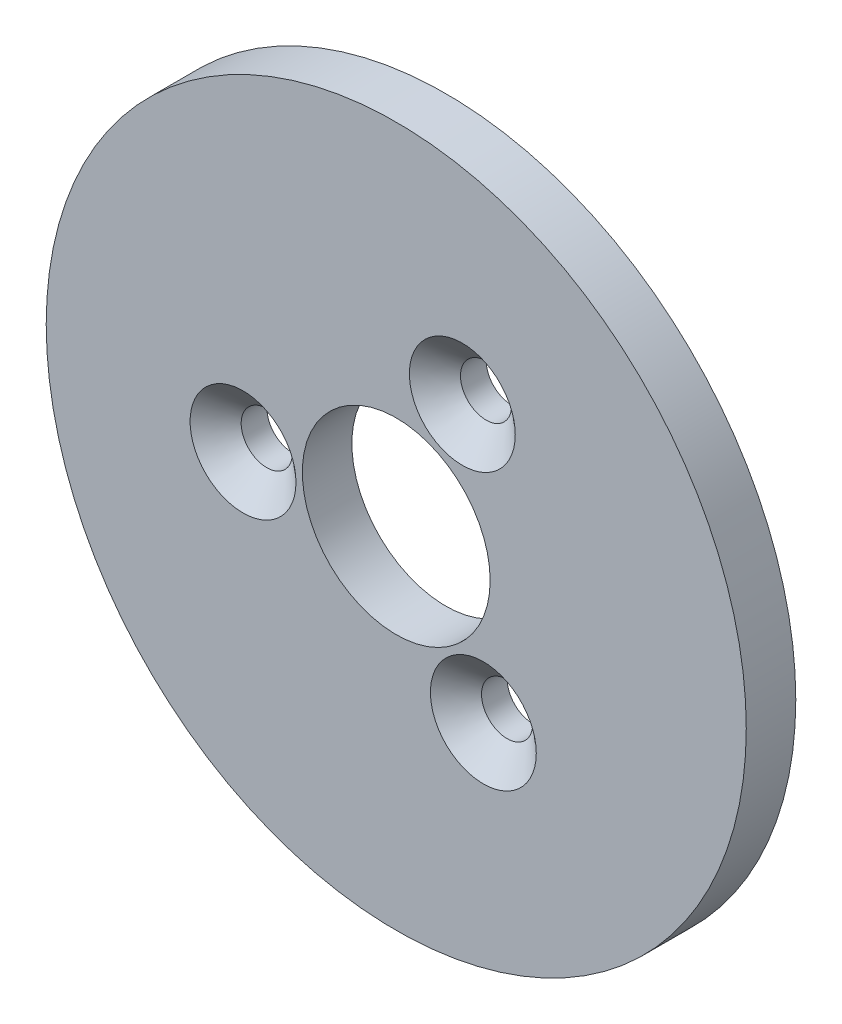
SolidWorks part; units mm, degrees
material "Acrylic (Medium-high impact)"
ref_plane "Front Plane" through (0, 0, 0) normal (0, 0, 1) x (1, 0, 0)
ref_plane "Top Plane" through (0, 0, 0) normal (0, 1, 0) x (1, 0, 0)
ref_plane "Right Plane" through (0, 0, 0) normal (1, 0, 0) x (0, 0, -1)
sketch "Sketch1" plane through (0, 0, 0) normal (0, 0, 1) x (1, 0, 0)
  circle A0 centre (0, 0) radius 20.5
  dimension "D1" = 41
extrude "Boss-Extrude1" add sketch "Sketch1" along normal blind 2.9
sketch "Sketch2" plane through (0, 0, 2.9) normal (0, 0, 1) x (1, 0, 0)
  circle A3 centre (-8.9719, -0.7111) radius 1.5
  circle A4 centre (-8.9719, -0.7111) radius 1.5
  circle A5 centre (5.1018, -7.4143) radius 1.5
  circle A6 centre (5.1018, -7.4143) radius 1.5
  circle A7 centre (3.8701, 8.1254) radius 1.5
  circle A8 centre (3.8701, 8.1254) radius 1.5
  dimension "D2" = 0
  dimension "D3" = 0
  dimension "D4" = 0
extrude "Cut-Extrude1" cut sketch "Sketch2" against normal through all
chamfer "Chamfer1" distance 1.6 angle 41 3 edges at (-7.4719, -0.7111, 2.9) (5.3701, 8.1254, 2.9) (6.6018, -7.4143, 2.9) first distance on face at (6.6018, -7.4143, 2.9)
sketch "Sketch3" plane through (0, 0, 2.9) normal (0, 0, 1) x (1, 0, 0)
  circle A1 centre (0, 0) radius 5.5
  circle A2 centre (0, 0) radius 5.5
  dimension "D1" = 0
extrude "Cut-Extrude2" cut sketch "Sketch3" against normal through all
equation "\"smallPulleyTeeth\"= 15"
equation "\"largePulleyTeeth\"= 30"
equation "\"eighthThick\"= 2.9mm"
equation "\"sixteenthThick\"= 1.7mm"
equation "\"quarterThick\"=6.0mm"
equation "\"OD\"= 145mm"
equation "\"puckAngle\"= 60.5deg"
equation "\"puckDiam\"= 76.5mm"
equation "\"axlePress\"= 5.9mm"
equation "\"press\"= 0.2mm"
equation "\"wheelClear\"= 0.3mm"
equation "\"10-32clear\"= 4.8mm"
equation "\"D1@Boss-Extrude1\"=\"eighthThick\""
equation "\"D1@Chamfer1\"=(6.5-\"6-32clear\")/2"
equation "\"6-32clear\"= 3.3mm"
equation "\"8-32clear\"= 4.0mm"
